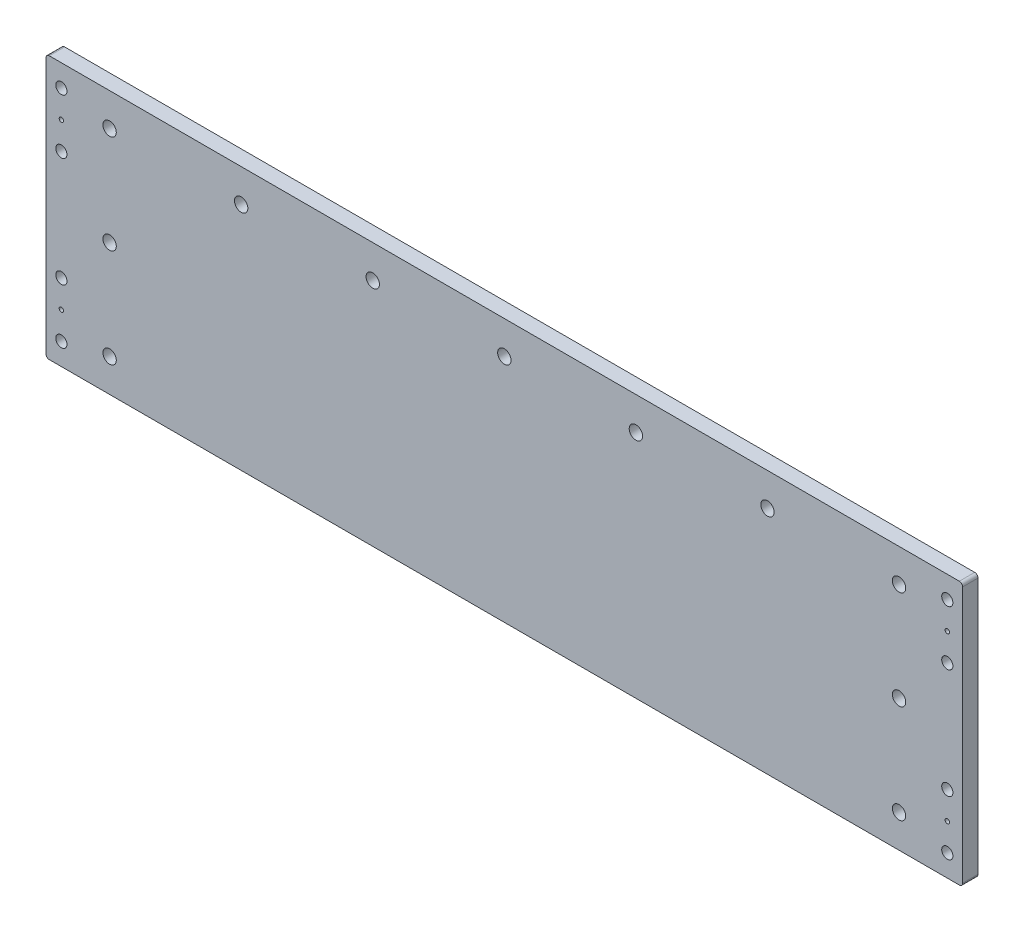
SolidWorks part; units mm, degrees
ref_plane "Front Plane" through (0, 0, 0) normal (0, 0, 1) x (1, 0, 0)
ref_plane "Top Plane" through (0, 0, 0) normal (0, 1, 0) x (1, 0, 0)
ref_plane "Right Plane" through (0, 0, 0) normal (1, 0, 0) x (0, 0, -1)
sketch "Sketch1" plane through (0, 0, 0) normal (0, 0, 1) x (1, 0, 0)
  line L1 (209, -60) -> (-209, -60)
  line L2 (209, -60) -> (209, 60)
  line L3 (209, 60) -> (-209, 60)
  line L4 (-209, -60) -> (-209, 60)
  line L5 (209, -60) -> (-209, 60) construction
  line L6 (209, 60) -> (-209, -60) construction
  point P0 (0, 0)
  dimension "D1" = 418
  dimension "D2" = 120
extrude "Boss-Extrude1" add sketch "Sketch1" along normal mid plane 7
sketch "Sketch3" plane through (0, 0, 3.5) normal (0, 0, 1) x (1, 0, 0)
  line L0 (-209, 45) -> (209, 45) construction
  line L1 (-209, 60) -> (-209, -60) construction
  line L2 (209, -60) -> (209, 60) construction
  line L3 (-209, -45) -> (209, -45) construction
  line L4 (-180, 60) -> (-180, -60) construction
  line L5 (209, 60) -> (-209, 60) construction
  line L6 (-209, -60) -> (209, -60) construction
  line L7 (180, 60) -> (180, -60) construction
  line L8 (-120, 60) -> (-120, -60) construction
  line L9 (120, 60) -> (120, -60) construction
  line L10 (-1000, 0) -> (49000, 0) construction
  circle A0 centre (-180, 45) radius 3.05
  circle A1 centre (180, 45) radius 3.05
  circle A2 centre (180, -45) radius 3.05
  circle A3 centre (-180, -45) radius 3.05
  circle A4 centre (0, 45) radius 3.05
  circle A5 centre (-120, 45) radius 3.05
  circle A6 centre (120, 45) radius 3.05
  circle A7 centre (-180, 0) radius 3.05
  circle A8 centre (-60, 45) radius 3.05
  circle A9 centre (60, 45) radius 3.05
  circle A10 centre (180, 0) radius 3.05
  dimension "D5" = 6.1
  dimension "D6" = 6.1
  dimension "D7" = 6.1
  dimension "D8" = 6.1
  dimension "D9" = 6.1
  dimension "D12" = 6.1
  dimension "D13" = 6.1
  dimension "D14" = 6.1
  dimension "D11" = 6.1
  dimension "D15" = 6.1
  dimension "D19" = 6.1
  dimension "D1" = 29
  dimension "D2" = 15
  dimension "D3" = 29
  dimension "D4" = 15
  dimension "D10" = 60
  dimension "D16" = 60
  dimension "D17" = 60
  dimension "D18" = 60
extrude "Cut-Extrude2" cut sketch "Sketch3" against normal through all
fillet "Fillet1" radius 1.5 4 edges at (-209, -60, 0) (209, -60, 0) (209, 60, 0) (-209, 60, 0)
sketch "Sketch4" plane through (0, 0, 3.5) normal (0, 0, 1) x (1, 0, 0)
  line L0 (-202, -1005.069) -> (-202, 48994.931) construction
  line L1 (-209, 58.5) -> (-209, -58.5) construction
  line L2 (207.5, 60) -> (-207.5, 60) construction
  circle A0 centre (-202, 50) radius 2.55
  circle A1 centre (-202, 37.5) radius 1
  circle A2 centre (-202, 25) radius 2.55
  dimension "D2" = 5.1
  dimension "D6" = 5.1
  dimension "D7" = 2
  dimension "D1" = 7
  dimension "D3" = 10
  dimension "D4" = 22.5
  dimension "D5" = 35
extrude "Cut-Extrude3" cut sketch "Sketch4" against normal through all
mirror "Mirror1" about plane through (0, 0, 0) normal (0, 1, 0) of "Cut-Extrude3"
mirror "Mirror2" about plane through (0, 0, 0) normal (1, 0, 0) of "Mirror1", "Cut-Extrude3"
equation "\"D6@Sketch3\"=6.1"
equation "\"D13@Sketch3\"=\"D6@Sketch3\""
equation "\"D9@Sketch3\"=\"D6@Sketch3\""
equation "\"D12@Sketch3\"=\"D6@Sketch3\""
equation "\"D7@Sketch3\"=\"D6@Sketch3\""
equation "\"D5@Sketch3\"=\"D6@Sketch3\""
equation "\"D8@Sketch3\"=\"D6@Sketch3\""
equation "\"D14@Sketch3\"=\"D6@Sketch3\""
equation "\"D1@Sketch3\"=15+14"
equation "\"D3@Sketch3\"=15+14"
equation "\"D11@Sketch3\"=\"D6@Sketch3\""
equation "\"D19@Sketch3\"=\"D6@Sketch3\""
